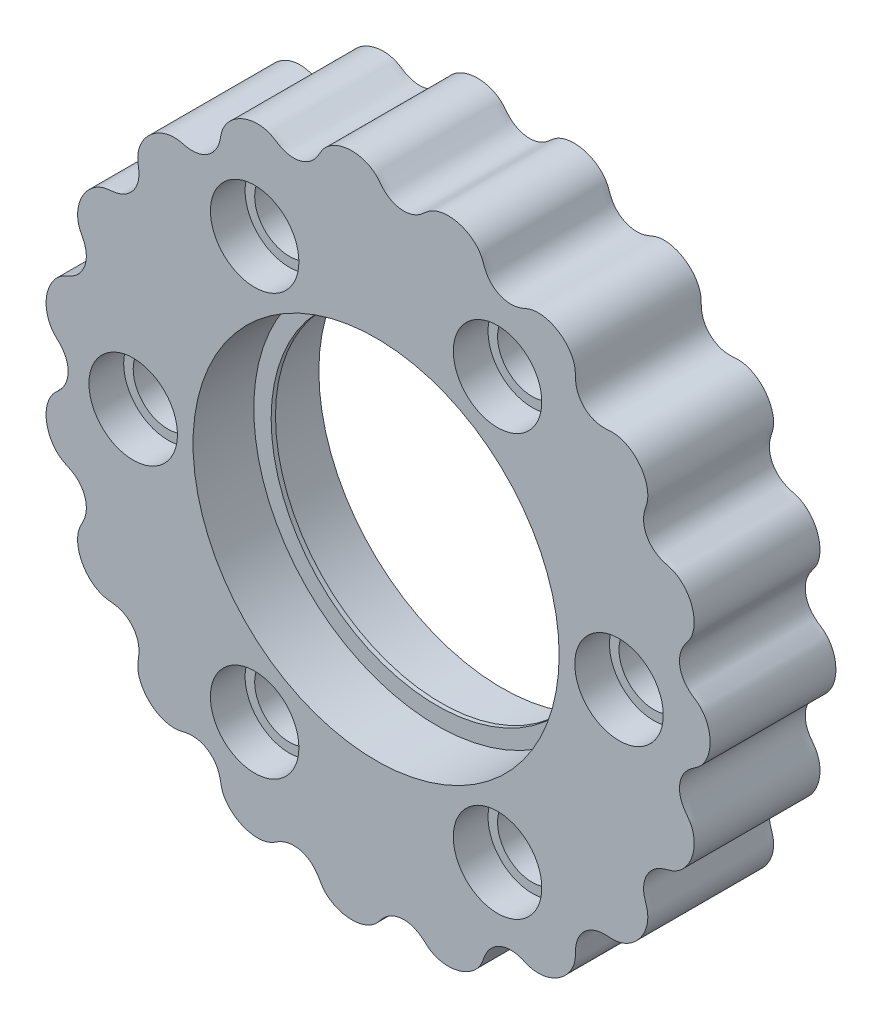
SolidWorks part; units mm, degrees
ref_plane "Front Plane" through (0, 0, 0) normal (0, 0, 1) x (1, 0, 0)
ref_plane "Top Plane" through (0, 0, 0) normal (0, 1, 0) x (1, 0, 0)
ref_plane "Right Plane" through (0, 0, 0) normal (1, 0, 0) x (0, 0, -1)
ref_axis "Axis1" through (0, 0, 55) along (0, 0, -1)
sketch "LobeBaseSketch" plane through (0, 0, 0) normal (0, 0, 1) x (1, 0, 0)
  spline S0 degree 3 poles (38.4912, -0.3506) (38.5044, 0) (38.4912, 0.3506) (38.4519, 0.6962) (38.3879, 1.0318) (38.3014, 1.353) (38.1951, 1.6558) (38.0727, 1.9368) (37.9379, 2.1933) (37.7949, 2.4237) (37.648, 2.6273) (37.5008, 2.8045) (37.3566, 2.9569) (37.2168, 3.0875) (37.0808, 3.2008) (36.9438, 3.304) (36.794, 3.4082) (36.6064, 3.5339) (36.3332, 3.724) (35.9067, 4.0748) (35.3443, 4.7509) (34.9315, 5.829) (34.9719, 6.9828) (35.2843, 7.8049) (35.5737, 8.2752) (35.7704, 8.5437) (35.9071, 8.7234) (36.0149, 8.8707) (36.111, 9.0127) (36.2028, 9.1641) (36.2926, 9.333) (36.3796, 9.5239) (36.4612, 9.7393) (36.5341, 9.9796) (36.5944, 10.2439) (36.6386, 10.5303) (36.6633, 10.8358) (36.6655, 11.1567) (36.643, 11.4886) (36.5945, 11.8269) (36.5195, 12.1665) (36.4181, 12.5024) (36.2918, 12.8297) (36.1425, 13.1438) (35.973, 13.4405) (35.7868, 13.7162) (35.588, 13.968) (35.3809, 14.194) (35.1701, 14.3929) (34.9601, 14.5644) (34.755, 14.7093) (34.5583, 14.8291) (34.3724, 14.9264) (34.1978, 15.0045) (34.0324, 15.0675) (33.8693, 15.1206) (33.6938, 15.1705) (33.4755, 15.2285) (33.1554, 15.3195) (32.6381, 15.5129) (31.8866, 15.9698) (31.1462, 16.8555) (30.8097, 17.9598) (30.8382, 18.8388) (30.9593, 19.3776) (31.0581, 19.6954) (31.129, 19.9098) (31.1832, 20.0841) (31.228, 20.2496) (31.2657, 20.4226) (31.2958, 20.6115) (31.316, 20.8203) (31.3233, 21.0505) (31.3142, 21.3015) (31.2855, 21.5711) (31.2343, 21.8563) (31.1584, 22.1533) (31.0562, 22.4575) (30.9272, 22.7641) (30.7716, 23.0683) (30.5903, 23.3651) (30.3854, 23.6499) (30.1596, 23.9184) (29.9164, 24.167) (29.6597, 24.3926) (29.3941, 24.5929) (29.1243, 24.7666) (28.8551, 24.9131) (28.5911, 25.0327) (28.3368, 25.1268) (28.0958, 25.1972) (27.8709, 25.2467) (27.6634, 25.2783) (27.4729, 25.2955) (27.296, 25.3014) (27.1245, 25.2987) (26.9423, 25.2889) (26.717, 25.2728) (26.3847, 25.255) (25.8327, 25.2699) (24.9735, 25.4581) (23.9856, 26.0553) (23.3088, 26.9905) (23.0504, 27.8312) (22.9899, 28.3801) (22.9802, 28.7128) (22.9777, 28.9386) (22.9723, 29.121) (22.9609, 29.2921) (22.9404, 29.468) (22.9076, 29.6564) (22.8589, 29.8605) (22.791, 30.0806) (22.7009, 30.315) (22.5862, 30.5607) (22.4452, 30.8138) (22.277, 31.07) (22.0816, 31.3246) (21.86, 31.5728) (21.614, 31.8099) (21.3462, 32.0318) (21.0599, 32.2346) (20.7592, 32.4153) (20.4484, 32.5714) (20.1324, 32.7015) (19.8162, 32.8047) (19.5046, 32.8813) (19.2024, 32.9325) (18.9139, 32.9599) (18.6428, 32.9663) (18.392, 32.9546) (18.1632, 32.9284) (17.9567, 32.891) (17.7709, 32.8454) (17.6017, 32.7935) (17.4404, 32.7353) (17.2712, 32.6668) (17.0633, 32.5785) (16.7548, 32.4537) (16.2278, 32.2886) (15.3542, 32.1876) (14.2259, 32.4317) (13.2821, 33.0965) (12.7647, 33.8077) (12.5293, 34.3072) (12.4121, 34.6187) (12.3363, 34.8315) (12.2721, 35.0023) (12.2057, 35.1604) (12.1292, 35.3201) (12.0369, 35.4876) (11.9246, 35.6649) (11.789, 35.851) (11.6277, 36.0434) (11.4394, 36.2385) (11.2238, 36.4322) (10.9815, 36.6199) (10.7141, 36.7972) (10.4239, 36.96) (10.1142, 37.1044) (9.7889, 37.2273) (9.4523, 37.3262) (9.1092, 37.3994) (8.7645, 37.4462) (8.4234, 37.4666) (8.0908, 37.4615) (7.7712, 37.4329) (7.4688, 37.3831) (7.187, 37.3154) (6.9285, 37.2334) (6.6951, 37.1409) (6.4872, 37.0418) (6.3041, 36.9394) (6.1432, 36.8359) (5.9999, 36.7319) (5.8663, 36.6245) (5.7285, 36.5048) (5.5606, 36.3538) (5.3093, 36.1356) (4.8645, 35.8083) (4.071, 35.4291) (2.9245, 35.2936) (1.816, 35.6159) (1.0957, 36.1206) (0.7109, 36.5166) (0.4989, 36.7732) (0.3582, 36.9498) (0.2419, 37.0905) (0.1278, 37.2185) (0.0036, 37.3447) (-0.1381, 37.4732) (-0.3018, 37.6044) (-0.4906, 37.7363) (-0.7056, 37.866) (-0.9471, 37.9894) (-1.2139, 38.1026) (-1.504, 38.2014) (-1.8145, 38.2823) (-2.1418, 38.342) (-2.4816, 38.3781) (-2.8292, 38.3887) (-3.1797, 38.3729) (-3.528, 38.3308) (-3.8691, 38.2631) (-4.1983, 38.1716) (-4.5113, 38.0588) (-4.8043, 37.928) (-5.0742, 37.7827) (-5.3187, 37.6272) (-5.5365, 37.4657) (-5.7273, 37.3024) (-5.8918, 37.1412) (-6.0317, 36.9848) (-6.1503, 36.8347) (-6.252, 36.6899) (-6.3435, 36.5448) (-6.435, 36.3869) (-6.5447, 36.1895) (-6.7116, 35.9016) (-7.026, 35.4476) (-7.6534, 34.8313) (-8.6938, 34.3309) (-9.8469, 34.2758) (-10.692, 34.5192) (-11.1846, 34.7688) (-11.4684, 34.9427) (-11.6588, 35.064) (-11.8145, 35.1594) (-11.964, 35.2434) (-12.1224, 35.3224) (-12.2981, 35.3979) (-12.4956, 35.4688) (-12.717, 35.5324) (-12.9625, 35.5852) (-13.2309, 35.6235) (-13.52, 35.6439) (-13.8265, 35.6432) (-14.1464, 35.6189) (-14.4754, 35.5691) (-14.8084, 35.4929) (-15.1407, 35.39) (-15.4671, 35.2613) (-15.7828, 35.1084) (-16.0835, 34.9336) (-16.3652, 34.7402) (-16.6246, 34.5319) (-16.8592, 34.313) (-17.0673, 34.0879) (-17.248, 33.8614) (-17.4016, 33.638) (-17.5291, 33.4216) (-17.6322, 33.2157) (-17.7138, 33.0224) (-17.7772, 32.8419) (-17.8264, 32.6719) (-17.8659, 32.505) (-17.9011, 32.3259) (-17.9409, 32.1036) (-18.0052, 31.7771) (-18.1551, 31.2456) (-18.5484, 30.4589) (-19.3699, 29.6479) (-20.4427, 29.2214) (-21.321, 29.1772) (-21.868, 29.2533) (-22.1929, 29.3256) (-22.4124, 29.3786) (-22.5906, 29.4182) (-22.7593, 29.4491) (-22.9347, 29.4724) (-23.1254, 29.4868) (-23.3353, 29.4897) (-23.5653, 29.478) (-23.8146, 29.4482) (-24.0809, 29.3973) (-24.361, 29.3227) (-24.6506, 29.2225) (-24.9454, 29.0956) (-25.2403, 28.9418) (-25.5306, 28.7615) (-25.8114, 28.5563) (-26.0783, 28.3286) (-26.3273, 28.0814) (-26.555, 27.8185) (-26.7586, 27.5441) (-26.9363, 27.2629) (-27.0871, 26.9796) (-27.2108, 26.6992) (-27.3083, 26.4263) (-27.381, 26.1651) (-27.4313, 25.9191) (-27.462, 25.6908) (-27.4764, 25.4815) (-27.4778, 25.2902) (-27.4691, 25.1134) (-27.4522, 24.9428) (-27.4274, 24.7619) (-27.3928, 24.5388) (-27.3476, 24.209) (-27.3169, 23.6577) (-27.4334, 22.7859) (-27.947, 21.7521) (-28.8232, 21.0004) (-29.6396, 20.6734) (-30.1817, 20.5678) (-30.5124, 20.5307) (-30.7372, 20.5095) (-30.9186, 20.4891) (-31.0882, 20.4635) (-31.2617, 20.4286) (-31.4468, 20.3803) (-31.6462, 20.3149) (-31.8599, 20.2291) (-32.0861, 20.12) (-32.3214, 19.9854) (-32.5621, 19.8239) (-32.8035, 19.6351) (-33.0411, 19.4194) (-33.2701, 19.1781) (-33.4861, 18.9133) (-33.6851, 18.6281) (-33.8636, 18.3261) (-34.0189, 18.0114) (-34.1488, 17.6888) (-34.2523, 17.3632) (-34.3291, 17.0395) (-34.3797, 16.7226) (-34.4057, 16.4172) (-34.4092, 16.1275) (-34.3932, 15.8568) (-34.3609, 15.6078) (-34.3158, 15.3819) (-34.2615, 15.1792) (-34.2007, 14.9979) (-34.135, 14.8335) (-34.0637, 14.6776) (-33.9815, 14.5146) (-33.8763, 14.3148) (-33.7265, 14.0176) (-33.5184, 13.506) (-33.3456, 12.6437) (-33.4957, 11.4991) (-34.0803, 10.5036) (-34.7463, 9.9293) (-35.2247, 9.6534) (-35.5255, 9.5109) (-35.7312, 9.4178) (-35.8962, 9.3397) (-36.0483, 9.2605) (-36.201, 9.171) (-36.3604, 9.0653) (-36.5278, 8.9387) (-36.7021, 8.7882) (-36.8805, 8.6115) (-37.0594, 8.4078) (-37.2346, 8.1769) (-37.4017, 7.9199) (-37.5563, 7.6388) (-37.6946, 7.3362) (-37.8129, 7.0156) (-37.9085, 6.6813) (-37.9793, 6.3376) (-38.0239, 5.9896) (-38.0421, 5.6423) (-38.0342, 5.3007) (-38.0017, 4.9696) (-37.9467, 4.6535) (-37.8722, 4.3562) (-37.7814, 4.081) (-37.6784, 3.8302) (-37.5669, 3.6051) (-37.451, 3.4062) (-37.3338, 3.2321) (-37.2174, 3.0803) (-37.1019, 2.9462) (-36.9838, 2.8218) (-36.8532, 2.6944) (-36.6888, 2.5395) (-36.4506, 2.3071) (-36.0877, 1.8908) (-35.6442, 1.1313) (-35.4145, 0) (-35.6442, -1.1313) (-36.0877, -1.8908) (-36.4506, -2.3071) (-36.6888, -2.5395) (-36.8532, -2.6944) (-36.9838, -2.8218) (-37.1019, -2.9462) (-37.2174, -3.0803) (-37.3338, -3.2321) (-37.451, -3.4062) (-37.5669, -3.6051) (-37.6784, -3.8302) (-37.7814, -4.081) (-37.8722, -4.3562) (-37.9467, -4.6535) (-38.0017, -4.9696) (-38.0342, -5.3007) (-38.0421, -5.6423) (-38.0239, -5.9896) (-37.9793, -6.3376) (-37.9085, -6.6813) (-37.8129, -7.0156) (-37.6946, -7.3362) (-37.5563, -7.6388) (-37.4017, -7.9199) (-37.2346, -8.1769) (-37.0594, -8.4078) (-36.8805, -8.6115) (-36.7021, -8.7882) (-36.5278, -8.9387) (-36.3604, -9.0653) (-36.201, -9.171) (-36.0483, -9.2605) (-35.8962, -9.3397) (-35.7312, -9.4178) (-35.5255, -9.5109) (-35.2247, -9.6534) (-34.7463, -9.9293) (-34.0803, -10.5036) (-33.4957, -11.4991) (-33.3456, -12.6437) (-33.5184, -13.506) (-33.7265, -14.0176) (-33.8763, -14.3148) (-33.9815, -14.5146) (-34.0637, -14.6776) (-34.135, -14.8335) (-34.2007, -14.9979) (-34.2615, -15.1792) (-34.3158, -15.3819) (-34.3609, -15.6078) (-34.3932, -15.8568) (-34.4092, -16.1275) (-34.4057, -16.4172) (-34.3797, -16.7226) (-34.3291, -17.0395) (-34.2523, -17.3632) (-34.1488, -17.6888) (-34.0189, -18.0114) (-33.8636, -18.3261) (-33.6851, -18.6281) (-33.4861, -18.9133) (-33.2701, -19.1781) (-33.0411, -19.4194) (-32.8035, -19.6351) (-32.5621, -19.8239) (-32.3214, -19.9854) (-32.0861, -20.12) (-31.8599, -20.2291) (-31.6462, -20.3149) (-31.4468, -20.3803) (-31.2617, -20.4286) (-31.0882, -20.4635) (-30.9186, -20.4891) (-30.7372, -20.5095) (-30.5124, -20.5307) (-30.1817, -20.5678) (-29.6396, -20.6734) (-28.8232, -21.0004) (-27.947, -21.7521) (-27.4334, -22.7859) (-27.3169, -23.6577) (-27.3476, -24.209) (-27.3928, -24.5388) (-27.4274, -24.7619) (-27.4522, -24.9428) (-27.4691, -25.1134) (-27.4778, -25.2902) (-27.4764, -25.4815) (-27.462, -25.6908) (-27.4313, -25.9191) (-27.381, -26.1651) (-27.3083, -26.4263) (-27.2108, -26.6992) (-27.0871, -26.9796) (-26.9363, -27.2629) (-26.7586, -27.5441) (-26.555, -27.8185) (-26.3273, -28.0814) (-26.0783, -28.3286) (-25.8114, -28.5563) (-25.5306, -28.7615) (-25.2403, -28.9418) (-24.9454, -29.0956) (-24.6506, -29.2225) (-24.361, -29.3227) (-24.0809, -29.3973) (-23.8146, -29.4482) (-23.5653, -29.478) (-23.3353, -29.4897) (-23.1254, -29.4868) (-22.9347, -29.4724) (-22.7593, -29.4491) (-22.5906, -29.4182) (-22.4124, -29.3786) (-22.1929, -29.3256) (-21.868, -29.2533) (-21.321, -29.1772) (-20.4427, -29.2214) (-19.3699, -29.6479) (-18.5484, -30.4589) (-18.1551, -31.2456) (-18.0052, -31.7771) (-17.9409, -32.1036) (-17.9011, -32.3259) (-17.8659, -32.505) (-17.8264, -32.6719) (-17.7772, -32.8419) (-17.7138, -33.0224) (-17.6322, -33.2157) (-17.5291, -33.4216) (-17.4016, -33.638) (-17.248, -33.8614) (-17.0673, -34.0879) (-16.8592, -34.313) (-16.6246, -34.5319) (-16.3652, -34.7402) (-16.0835, -34.9336) (-15.7828, -35.1084) (-15.4671, -35.2613) (-15.1407, -35.39) (-14.8084, -35.4929) (-14.4754, -35.5691) (-14.1464, -35.6189) (-13.8265, -35.6432) (-13.52, -35.6439) (-13.2309, -35.6235) (-12.9625, -35.5852) (-12.717, -35.5324) (-12.4956, -35.4688) (-12.2981, -35.3979) (-12.1224, -35.3224) (-11.964, -35.2434) (-11.8145, -35.1594) (-11.6588, -35.064) (-11.4684, -34.9427) (-11.1846, -34.7688) (-10.692, -34.5192) (-9.8469, -34.2758) (-8.6938, -34.3309) (-7.6534, -34.8313) (-7.026, -35.4476) (-6.7116, -35.9016) (-6.5447, -36.1895) (-6.435, -36.3869) (-6.3435, -36.5448) (-6.252, -36.6899) (-6.1503, -36.8347) (-6.0317, -36.9848) (-5.8918, -37.1412) (-5.7273, -37.3024) (-5.5365, -37.4657) (-5.3187, -37.6272) (-5.0742, -37.7827) (-4.8043, -37.928) (-4.5113, -38.0588) (-4.1983, -38.1716) (-3.8691, -38.2631) (-3.528, -38.3308) (-3.1797, -38.3729) (-2.8292, -38.3887) (-2.4816, -38.3781) (-2.1418, -38.342) (-1.8145, -38.2823) (-1.504, -38.2014) (-1.2139, -38.1026) (-0.9471, -37.9894) (-0.7056, -37.866) (-0.4906, -37.7363) (-0.3018, -37.6044) (-0.1381, -37.4732) (0.0036, -37.3447) (0.1278, -37.2185) (0.2419, -37.0905) (0.3582, -36.9498) (0.4989, -36.7732) (0.7109, -36.5166) (1.0957, -36.1206) (1.816, -35.6159) (2.9245, -35.2936) (4.071, -35.4291) (4.8645, -35.8083) (5.3093, -36.1356) (5.5606, -36.3538) (5.7285, -36.5048) (5.8663, -36.6245) (5.9999, -36.7319) (6.1432, -36.8359) (6.3041, -36.9394) (6.4872, -37.0418) (6.6951, -37.1409) (6.9285, -37.2334) (7.187, -37.3154) (7.4688, -37.3831) (7.7712, -37.4329) (8.0908, -37.4615) (8.4234, -37.4666) (8.7645, -37.4462) (9.1092, -37.3994) (9.4523, -37.3262) (9.7889, -37.2273) (10.1142, -37.1044) (10.4239, -36.96) (10.7141, -36.7972) (10.9815, -36.6199) (11.2238, -36.4322) (11.4394, -36.2385) (11.6277, -36.0434) (11.789, -35.851) (11.9246, -35.6649) (12.0369, -35.4876) (12.1292, -35.3201) (12.2057, -35.1604) (12.2721, -35.0023) (12.3363, -34.8315) (12.4121, -34.6187) (12.5293, -34.3072) (12.7647, -33.8077) (13.2821, -33.0965) (14.2259, -32.4317) (15.3542, -32.1876) (16.2278, -32.2886) (16.7548, -32.4537) (17.0633, -32.5785) (17.2712, -32.6668) (17.4404, -32.7353) (17.6017, -32.7935) (17.7709, -32.8454) (17.9567, -32.891) (18.1632, -32.9284) (18.392, -32.9546) (18.6428, -32.9663) (18.9139, -32.9599) (19.2024, -32.9325) (19.5046, -32.8813) (19.8162, -32.8047) (20.1324, -32.7015) (20.4484, -32.5714) (20.7592, -32.4153) (21.0599, -32.2346) (21.3462, -32.0318) (21.614, -31.8099) (21.86, -31.5728) (22.0816, -31.3246) (22.277, -31.07) (22.4452, -30.8138) (22.5862, -30.5607) (22.7009, -30.315) (22.791, -30.0806) (22.8589, -29.8605) (22.9076, -29.6564) (22.9404, -29.468) (22.9609, -29.2921) (22.9723, -29.121) (22.9777, -28.9386) (22.9802, -28.7128) (22.9899, -28.3801) (23.0504, -27.8312) (23.3088, -26.9905) (23.9856, -26.0553) (24.9735, -25.4581) (25.8327, -25.2699) (26.3847, -25.255) (26.717, -25.2728) (26.9423, -25.2889) (27.1245, -25.2987) (27.296, -25.3014) (27.4729, -25.2955) (27.6634, -25.2783) (27.8709, -25.2467) (28.0958, -25.1972) (28.3368, -25.1268) (28.5911, -25.0327) (28.8551, -24.9131) (29.1243, -24.7666) (29.3941, -24.5929) (29.6597, -24.3926) (29.9164, -24.167) (30.1596, -23.9184) (30.3854, -23.6499) (30.5903, -23.3651) (30.7716, -23.0683) (30.9272, -22.7641) (31.0562, -22.4575) (31.1584, -22.1533) (31.2343, -21.8563) (31.2855, -21.5711) (31.3142, -21.3015) (31.3233, -21.0505) (31.316, -20.8203) (31.2958, -20.6115) (31.2657, -20.4226) (31.228, -20.2496) (31.1832, -20.0841) (31.129, -19.9098) (31.0581, -19.6954) (30.9593, -19.3776) (30.8382, -18.8388) (30.8097, -17.9598) (31.1462, -16.8555) (31.8866, -15.9698) (32.6381, -15.5129) (33.1554, -15.3195) (33.4755, -15.2285) (33.6938, -15.1705) (33.8693, -15.1206) (34.0324, -15.0675) (34.1978, -15.0045) (34.3724, -14.9264) (34.5583, -14.8291) (34.755, -14.7093) (34.9601, -14.5644) (35.1701, -14.3929) (35.3809, -14.194) (35.588, -13.968) (35.7868, -13.7162) (35.973, -13.4405) (36.1425, -13.1438) (36.2918, -12.8297) (36.4181, -12.5024) (36.5195, -12.1665) (36.5945, -11.8269) (36.643, -11.4886) (36.6655, -11.1567) (36.6633, -10.8358) (36.6386, -10.5303) (36.5944, -10.2439) (36.5341, -9.9796) (36.4612, -9.7393) (36.3796, -9.5239) (36.2926, -9.333) (36.2028, -9.1641) (36.111, -9.0127) (36.0149, -8.8707) (35.9071, -8.7234) (35.7704, -8.5437) (35.5737, -8.2752) (35.2843, -7.8049) (34.9719, -6.9828) (34.9315, -5.829) (35.3443, -4.7509) (35.9067, -4.0748) (36.3332, -3.724) (36.6064, -3.5339) (36.794, -3.4082) (36.9438, -3.304) (37.0808, -3.2008) (37.2168, -3.0875) (37.3566, -2.9569) (37.5008, -2.8045) (37.648, -2.6273) (37.7949, -2.4237) (37.9379, -2.1933) (38.0727, -1.9368) (38.1951, -1.6558) (38.3014, -1.353) (38.3879, -1.0318) (38.4519, -0.6962) (38.4912, -0.3506) (38.5044, 0) (38.4912, 0.3506) knots -0.003877 -0.002604 -0.001308 0 0.001308 0.002604 0.003877 0.005117 0.006313 0.007454 0.008534 0.009543 0.010478 0.011334 0.012112 0.012818 0.013466 0.014086 0.014731 0.015503 0.016606 0.018444 0.021651 0.026316 0.03098 0.034188 0.036026 0.037129 0.037901 0.038546 0.039165 0.039814 0.04052 0.041298 0.042154 0.043088 0.044098 0.045177 0.046319 0.047515 0.048754 0.050028 0.051324 0.052632 0.053939 0.055235 0.056509 0.057748 0.058944 0.060086 0.061165 0.062175 0.063109 0.063965 0.064743 0.065449 0.066098 0.066718 0.067362 0.068134 0.069238 0.071075 0.074283 0.078947 0.083612 0.08682 0.088657 0.08976 0.090533 0.091177 0.091797 0.092445 0.093152 0.09393 0.094785 0.09572 0.096729 0.097809 0.098951 0.100146 0.101386 0.102659 0.103956 0.105263 0.106571 0.107867 0.10914 0.11038 0.111576 0.112718 0.113797 0.114807 0.115741 0.116597 0.117375 0.118081 0.11873 0.119349 0.119994 0.120766 0.121869 0.123707 0.126914 0.131579 0.136243 0.139451 0.141289 0.142392 0.143164 0.143809 0.144428 0.145077 0.145783 0.146561 0.147417 0.148351 0.149361 0.15044 0.151582 0.152778 0.154018 0.155291 0.156587 0.157895 0.159202 0.160498 0.161772 0.163012 0.164207 0.165349 0.166429 0.167438 0.168372 0.169228 0.170006 0.170712 0.171361 0.171981 0.172625 0.173398 0.174501 0.176338 0.179546 0.184211 0.188875 0.192083 0.19392 0.195023 0.195796 0.19644 0.19706 0.197709 0.198415 0.199193 0.200049 0.200983 0.201992 0.203072 0.204214 0.205409 0.206649 0.207923 0.209219 0.210526 0.211834 0.21313 0.214403 0.215643 0.216839 0.217981 0.21906 0.22007 0.221004 0.22186 0.222638 0.223344 0.223993 0.224612 0.225257 0.226029 0.227132 0.22897 0.232178 0.236842 0.241507 0.244714 0.246552 0.247655 0.248427 0.249072 0.249692 0.25034 0.251046 0.251824 0.25268 0.253614 0.254624 0.255703 0.256845 0.258041 0.259281 0.260554 0.26185 0.263158 0.264465 0.265762 0.267035 0.268275 0.26947 0.270612 0.271692 0.272701 0.273636 0.274491 0.275269 0.275976 0.276624 0.277244 0.277888 0.278661 0.279764 0.281602 0.284809 0.289474 0.294138 0.297346 0.299183 0.300287 0.301059 0.301703 0.302323 0.302972 0.303678 0.304456 0.305312 0.306246 0.307256 0.308335 0.309477 0.310673 0.311912 0.313186 0.314482 0.315789 0.317097 0.318393 0.319667 0.320906 0.322102 0.323244 0.324323 0.325333 0.326267 0.327123 0.327901 0.328607 0.329256 0.329876 0.33052 0.331292 0.332395 0.334233 0.337441 0.342105 0.34677 0.349977 0.351815 0.352918 0.35369 0.354335 0.354955 0.355603 0.35631 0.357088 0.357943 0.358878 0.359887 0.360967 0.362109 0.363304 0.364544 0.365817 0.367113 0.368421 0.369729 0.371025 0.372298 0.373538 0.374734 0.375875 0.376955 0.377965 0.378899 0.379755 0.380533 0.381239 0.381887 0.382507 0.383152 0.383924 0.385027 0.386865 0.390072 0.394737 0.399401 0.402609 0.404447 0.40555 0.406322 0.406967 0.407586 0.408235 0.408941 0.409719 0.410575 0.411509 0.412519 0.413598 0.41474 0.415936 0.417176 0.418449 0.419745 0.421053 0.42236 0.423656 0.42493 0.426169 0.427365 0.428507 0.429586 0.430596 0.43153 0.432386 0.433164 0.43387 0.434519 0.435139 0.435783 0.436556 0.437659 0.439496 0.442704 0.447368 0.452033 0.455241 0.457078 0.458181 0.458954 0.459598 0.460218 0.460867 0.461573 0.462351 0.463207 0.464141 0.46515 0.46623 0.467372 0.468567 0.469807 0.471081 0.472377 0.473684 0.474992 0.476288 0.477561 0.478801 0.479997 0.481139 0.482218 0.483228 0.484162 0.485018 0.485796 0.486502 0.487151 0.48777 0.488415 0.489187 0.49029 0.492128 0.495336 0.5 0.504664 0.507872 0.50971 0.510813 0.511585 0.51223 0.512849 0.513498 0.514204 0.514982 0.515838 0.516772 0.517782 0.518861 0.520003 0.521199 0.522439 0.523712 0.525008 0.526316 0.527623 0.528919 0.530193 0.531433 0.532628 0.53377 0.53485 0.535859 0.536793 0.537649 0.538427 0.539133 0.539782 0.540402 0.541046 0.541819 0.542922 0.544759 0.547967 0.552632 0.557296 0.560504 0.562341 0.563444 0.564217 0.564861 0.565481 0.56613 0.566836 0.567614 0.56847 0.569404 0.570414 0.571493 0.572635 0.573831 0.57507 0.576344 0.57764 0.578947 0.580255 0.581551 0.582824 0.584064 0.58526 0.586402 0.587481 0.588491 0.589425 0.590281 0.591059 0.591765 0.592414 0.593033 0.593678 0.59445 0.595553 0.597391 0.600599 0.605263 0.609928 0.613135 0.614973 0.616076 0.616848 0.617493 0.618113 0.618761 0.619467 0.620245 0.621101 0.622035 0.623045 0.624125 0.625266 0.626462 0.627702 0.628975 0.630271 0.631579 0.632887 0.634183 0.635456 0.636696 0.637891 0.639033 0.640113 0.641122 0.642057 0.642912 0.64369 0.644397 0.645045 0.645665 0.64631 0.647082 0.648185 0.650023 0.65323 0.657895 0.662559 0.665767 0.667605 0.668708 0.66948 0.670124 0.670744 0.671393 0.672099 0.672877 0.673733 0.674667 0.675677 0.676756 0.677898 0.679094 0.680333 0.681607 0.682903 0.684211 0.685518 0.686814 0.688088 0.689327 0.690523 0.691665 0.692744 0.693754 0.694688 0.695544 0.696322 0.697028 0.697677 0.698297 0.698941 0.699713 0.700817 0.702654 0.705862 0.710526 0.715191 0.718398 0.720236 0.721339 0.722112 0.722756 0.723376 0.724024 0.724731 0.725509 0.726364 0.727299 0.728308 0.729388 0.73053 0.731725 0.732965 0.734238 0.735535 0.736842 0.73815 0.739446 0.740719 0.741959 0.743155 0.744297 0.745376 0.746386 0.74732 0.748176 0.748954 0.74966 0.750308 0.750928 0.751573 0.752345 0.753448 0.755286 0.758493 0.763158 0.767822 0.77103 0.772868 0.773971 0.774743 0.775388 0.776007 0.776656 0.777362 0.77814 0.778996 0.77993 0.78094 0.782019 0.783161 0.784357 0.785597 0.78687 0.788166 0.789474 0.790781 0.792077 0.793351 0.794591 0.795786 0.796928 0.798008 0.799017 0.799951 0.800807 0.801585 0.802291 0.80294 0.80356 0.804204 0.804977 0.80608 0.807917 0.811125 0.815789 0.820454 0.823662 0.825499 0.826602 0.827375 0.828019 0.828639 0.829288 0.829994 0.830772 0.831628 0.832562 0.833571 0.834651 0.835793 0.836988 0.838228 0.839502 0.840798 0.842105 0.843413 0.844709 0.845982 0.847222 0.848418 0.84956 0.850639 0.851649 0.852583 0.853439 0.854217 0.854923 0.855572 0.856191 0.856836 0.857608 0.858711 0.860549 0.863757 0.868421 0.873086 0.876293 0.878131 0.879234 0.880006 0.880651 0.88127 0.881919 0.882625 0.883403 0.884259 0.885193 0.886203 0.887282 0.888424 0.88962 0.89086 0.892133 0.893429 0.894737 0.896044 0.897341 0.898614 0.899854 0.901049 0.902191 0.903271 0.90428 0.905215 0.90607 0.906848 0.907555 0.908203 0.908823 0.909467 0.91024 0.911343 0.91318 0.916388 0.921053 0.925717 0.928925 0.930762 0.931866 0.932638 0.933282 0.933902 0.934551 0.935257 0.936035 0.936891 0.937825 0.938835 0.939914 0.941056 0.942252 0.943491 0.944765 0.946061 0.947368 0.948676 0.949972 0.951246 0.952485 0.953681 0.954823 0.955902 0.956912 0.957846 0.958702 0.95948 0.960186 0.960835 0.961454 0.962099 0.962871 0.963974 0.965812 0.96902 0.973684 0.978349 0.981556 0.983394 0.984497 0.985269 0.985914 0.986534 0.987182 0.987888 0.988666 0.989522 0.990457 0.991466 0.992546 0.993687 0.994883 0.996123 0.997396 0.998692 1 1.001308 1.002604 1.003877 only from (38.5, 0) to (38.5, 0)
extrude "LobeBase" add sketch "LobeBaseSketch" along normal blind 7.25 and the other way blind 7.25
sketch "AuxiliarySketchCycloidal01" plane through (0, 0, 0) normal (0, 0, 1) x (1, 0, 0)
  circle A0 centre (0, 0) radius 38 construction
  circle A1 centre (40, 0) radius 2 construction
  circle A2 centre (0, 0) radius 40 construction
  circle A3 centre (40, 0) radius 3 construction
  circle A4 centre (41.5, 0) radius 0.3 construction
  spline S0 degree 3 poles (41.5, 0) (41.5, 0.3843) (41.4568, 0.9578) (41.3145, 1.7041) (41.1697, 2.2415) (40.9899, 2.7537) (40.7798, 3.2358) (40.5445, 3.6835) (40.2901, 4.0936) (40.023, 4.4639) (39.7497, 4.7932) (39.4771, 5.0816) (39.2117, 5.3301) (38.96, 5.5408) (38.7277, 5.7169) (38.5202, 5.8624) (38.3419, 5.9822) (38.1959, 6.0818) (38.0845, 6.1679) (38.007, 6.248) (37.9674, 6.3356) (37.9764, 6.4314) (38.0237, 6.5323) (38.1012, 6.6499) (38.2068, 6.7915) (38.3366, 6.9628) (38.4856, 7.1678) (38.6481, 7.4097) (38.8178, 7.6907) (38.9881, 8.0119) (39.1523, 8.3732) (39.3039, 8.7734) (39.4363, 9.2104) (39.5437, 9.6809) (39.6209, 10.1807) (39.6631, 10.7049) (39.6668, 11.2477) (39.6293, 11.803) (39.5215, 12.5551) (39.3762, 13.1116) (39.2514, 13.475) knots 0 0 0 0 0.076019 0.113454 0.150205 0.18605 0.220775 0.25417 0.286039 0.316192 0.344454 0.370663 0.394671 0.41635 0.435595 0.452323 0.466491 0.478109 0.487286 0.494331 0.5 0.505669 0.512714 0.521891 0.533509 0.547677 0.564405 0.58365 0.605329 0.629337 0.655546 0.683808 0.713961 0.74583 0.779225 0.81395 0.849795 0.886546 0.923981 1 1 1 1 construction
sketch "Sketch5" plane through (0, 0, 7.25) normal (0, 0, 1) x (1, 0, 0)
  circle A0 centre (0, 0) radius 21.1
  dimension "D1" = 42.2
extrude "Cut-Extrude1" cut sketch "Sketch5" against normal blind 7
sketch "Sketch6" plane through (0, 0, -7.25) normal (0, 0, -1) x (-1, 0, 0)
  circle A0 centre (0, 0) radius 21.1
  dimension "D1" = 42.2
extrude "Cut-Extrude2" cut sketch "Sketch6" against normal blind 7
sketch "Sketch7" plane through (0, 0, 7.25) normal (0, 0, 1) x (1, 0, 0)
  circle A0 centre (0, 0) radius 19.1
  circle A1 centre (0, 0) radius 21.1 construction
  dimension "D1" = 2
extrude "Cut-Extrude3" cut sketch "Sketch7" against normal through all
sketch "Sketch8" plane through (0, 0, 7.25) normal (0, 0, 1) x (1, 0, 0)
  circle A0 centre (28, 0) radius 5.1
  dimension "D2" = 10.2
extrude "Cut-Extrude4" cut sketch "Sketch8" against normal blind 4
sketch "Sketch10" plane through (0, 0, -7.25) normal (0, 0, -1) x (-1, 0, 0)
  circle A0 centre (-28, 0) radius 4
  dimension "D1" = 8
extrude "Cut-Extrude5" cut sketch "Sketch10" against normal through all
pattern_circular "CirPattern1" count 6 over 360 about axis through (0, 0, 7.25) along (0, 0, 1) of "Cut-Extrude4", "Cut-Extrude5"
sketch "Sketch11" plane through (0, 0, 7.25) normal (0, 0, 1) x (1, 0, 0)
  line L0 (38.5, 0) -> (-35.5, 0) construction
  spline S0 degree 3 poles (38.4912, -0.3506) (38.5044, 0) (38.4912, 0.3506) (38.4519, 0.6962) (38.3879, 1.0318) (38.3014, 1.353) (38.1951, 1.6558) (38.0727, 1.9368) (37.9379, 2.1933) (37.7949, 2.4237) (37.648, 2.6273) (37.5008, 2.8045) (37.3566, 2.9569) (37.2168, 3.0875) (37.0808, 3.2008) (36.9438, 3.304) (36.794, 3.4082) (36.6064, 3.5339) (36.3332, 3.724) (35.9067, 4.0748) (35.3443, 4.7509) (34.9315, 5.829) (34.9719, 6.9828) (35.2843, 7.8049) (35.5737, 8.2752) (35.7704, 8.5437) (35.9071, 8.7234) (36.0149, 8.8707) (36.111, 9.0127) (36.2028, 9.1641) (36.2926, 9.333) (36.3796, 9.5239) (36.4612, 9.7393) (36.5341, 9.9796) (36.5944, 10.2439) (36.6386, 10.5303) (36.6633, 10.8358) (36.6655, 11.1567) (36.643, 11.4886) (36.5945, 11.8269) (36.5195, 12.1665) (36.4181, 12.5024) (36.2918, 12.8297) (36.1425, 13.1438) (35.973, 13.4405) (35.7868, 13.7162) (35.588, 13.968) (35.3809, 14.194) (35.1701, 14.3929) (34.9601, 14.5644) (34.755, 14.7093) (34.5583, 14.8291) (34.3724, 14.9264) (34.1978, 15.0045) (34.0324, 15.0675) (33.8693, 15.1206) (33.6938, 15.1705) (33.4755, 15.2285) (33.1554, 15.3195) (32.6381, 15.5129) (31.8866, 15.9698) (31.1462, 16.8555) (30.8097, 17.9598) (30.8382, 18.8388) (30.9593, 19.3776) (31.0581, 19.6954) (31.129, 19.9098) (31.1832, 20.0841) (31.228, 20.2496) (31.2657, 20.4226) (31.2958, 20.6115) (31.316, 20.8203) (31.3233, 21.0505) (31.3142, 21.3015) (31.2855, 21.5711) (31.2343, 21.8563) (31.1584, 22.1533) (31.0562, 22.4575) (30.9272, 22.7641) (30.7716, 23.0683) (30.5903, 23.3651) (30.3854, 23.6499) (30.1596, 23.9184) (29.9164, 24.167) (29.6597, 24.3926) (29.3941, 24.5929) (29.1243, 24.7666) (28.8551, 24.9131) (28.5911, 25.0327) (28.3368, 25.1268) (28.0958, 25.1972) (27.8709, 25.2467) (27.6634, 25.2783) (27.4729, 25.2955) (27.296, 25.3014) (27.1245, 25.2987) (26.9423, 25.2889) (26.717, 25.2728) (26.3847, 25.255) (25.8327, 25.2699) (24.9735, 25.4581) (23.9856, 26.0553) (23.3088, 26.9905) (23.0504, 27.8312) (22.9899, 28.3801) (22.9802, 28.7128) (22.9777, 28.9386) (22.9723, 29.121) (22.9609, 29.2921) (22.9404, 29.468) (22.9076, 29.6564) (22.8589, 29.8605) (22.791, 30.0806) (22.7009, 30.315) (22.5862, 30.5607) (22.4452, 30.8138) (22.277, 31.07) (22.0816, 31.3246) (21.86, 31.5728) (21.614, 31.8099) (21.3462, 32.0318) (21.0599, 32.2346) (20.7592, 32.4153) (20.4484, 32.5714) (20.1324, 32.7015) (19.8162, 32.8047) (19.5046, 32.8813) (19.2024, 32.9325) (18.9139, 32.9599) (18.6428, 32.9663) (18.392, 32.9546) (18.1632, 32.9284) (17.9567, 32.891) (17.7709, 32.8454) (17.6017, 32.7935) (17.4404, 32.7353) (17.2712, 32.6668) (17.0633, 32.5785) (16.7548, 32.4537) (16.2278, 32.2886) (15.3542, 32.1876) (14.2259, 32.4317) (13.2821, 33.0965) (12.7647, 33.8077) (12.5293, 34.3072) (12.4121, 34.6187) (12.3363, 34.8315) (12.2721, 35.0023) (12.2057, 35.1604) (12.1292, 35.3201) (12.0369, 35.4876) (11.9246, 35.6649) (11.789, 35.851) (11.6277, 36.0434) (11.4394, 36.2385) (11.2238, 36.4322) (10.9815, 36.6199) (10.7141, 36.7972) (10.4239, 36.96) (10.1142, 37.1044) (9.7889, 37.2273) (9.4523, 37.3262) (9.1092, 37.3994) (8.7645, 37.4462) (8.4234, 37.4666) (8.0908, 37.4615) (7.7712, 37.4329) (7.4688, 37.3831) (7.187, 37.3154) (6.9285, 37.2334) (6.6951, 37.1409) (6.4872, 37.0418) (6.3041, 36.9394) (6.1432, 36.8359) (5.9999, 36.7319) (5.8663, 36.6245) (5.7285, 36.5048) (5.5606, 36.3538) (5.3093, 36.1356) (4.8645, 35.8083) (4.071, 35.4291) (2.9245, 35.2936) (1.816, 35.6159) (1.0957, 36.1206) (0.7109, 36.5166) (0.4989, 36.7732) (0.3582, 36.9498) (0.2419, 37.0905) (0.1278, 37.2185) (0.0036, 37.3447) (-0.1381, 37.4732) (-0.3018, 37.6044) (-0.4906, 37.7363) (-0.7056, 37.866) (-0.9471, 37.9894) (-1.2139, 38.1026) (-1.504, 38.2014) (-1.8145, 38.2823) (-2.1418, 38.342) (-2.4816, 38.3781) (-2.8292, 38.3887) (-3.1797, 38.3729) (-3.528, 38.3308) (-3.8691, 38.2631) (-4.1983, 38.1716) (-4.5113, 38.0588) (-4.8043, 37.928) (-5.0742, 37.7827) (-5.3187, 37.6272) (-5.5365, 37.4657) (-5.7273, 37.3024) (-5.8918, 37.1412) (-6.0317, 36.9848) (-6.1503, 36.8347) (-6.252, 36.6899) (-6.3435, 36.5448) (-6.435, 36.3869) (-6.5447, 36.1895) (-6.7116, 35.9016) (-7.026, 35.4476) (-7.6534, 34.8313) (-8.6938, 34.3309) (-9.8469, 34.2758) (-10.692, 34.5192) (-11.1846, 34.7688) (-11.4684, 34.9427) (-11.6588, 35.064) (-11.8145, 35.1594) (-11.964, 35.2434) (-12.1224, 35.3224) (-12.2981, 35.3979) (-12.4956, 35.4688) (-12.717, 35.5324) (-12.9625, 35.5852) (-13.2309, 35.6235) (-13.52, 35.6439) (-13.8265, 35.6432) (-14.1464, 35.6189) (-14.4754, 35.5691) (-14.8084, 35.4929) (-15.1407, 35.39) (-15.4671, 35.2613) (-15.7828, 35.1084) (-16.0835, 34.9336) (-16.3652, 34.7402) (-16.6246, 34.5319) (-16.8592, 34.313) (-17.0673, 34.0879) (-17.248, 33.8614) (-17.4016, 33.638) (-17.5291, 33.4216) (-17.6322, 33.2157) (-17.7138, 33.0224) (-17.7772, 32.8419) (-17.8264, 32.6719) (-17.8659, 32.505) (-17.9011, 32.3259) (-17.9409, 32.1036) (-18.0052, 31.7771) (-18.1551, 31.2456) (-18.5484, 30.4589) (-19.3699, 29.6479) (-20.4427, 29.2214) (-21.321, 29.1772) (-21.868, 29.2533) (-22.1929, 29.3256) (-22.4124, 29.3786) (-22.5906, 29.4182) (-22.7593, 29.4491) (-22.9347, 29.4724) (-23.1254, 29.4868) (-23.3353, 29.4897) (-23.5653, 29.478) (-23.8146, 29.4482) (-24.0809, 29.3973) (-24.361, 29.3227) (-24.6506, 29.2225) (-24.9454, 29.0956) (-25.2403, 28.9418) (-25.5306, 28.7615) (-25.8114, 28.5563) (-26.0783, 28.3286) (-26.3273, 28.0814) (-26.555, 27.8185) (-26.7586, 27.5441) (-26.9363, 27.2629) (-27.0871, 26.9796) (-27.2108, 26.6992) (-27.3083, 26.4263) (-27.381, 26.1651) (-27.4313, 25.9191) (-27.462, 25.6908) (-27.4764, 25.4815) (-27.4778, 25.2902) (-27.4691, 25.1134) (-27.4522, 24.9428) (-27.4274, 24.7619) (-27.3928, 24.5388) (-27.3476, 24.209) (-27.3169, 23.6577) (-27.4334, 22.7859) (-27.947, 21.7521) (-28.8232, 21.0004) (-29.6396, 20.6734) (-30.1817, 20.5678) (-30.5124, 20.5307) (-30.7372, 20.5095) (-30.9186, 20.4891) (-31.0882, 20.4635) (-31.2617, 20.4286) (-31.4468, 20.3803) (-31.6462, 20.3149) (-31.8599, 20.2291) (-32.0861, 20.12) (-32.3214, 19.9854) (-32.5621, 19.8239) (-32.8035, 19.6351) (-33.0411, 19.4194) (-33.2701, 19.1781) (-33.4861, 18.9133) (-33.6851, 18.6281) (-33.8636, 18.3261) (-34.0189, 18.0114) (-34.1488, 17.6888) (-34.2523, 17.3632) (-34.3291, 17.0395) (-34.3797, 16.7226) (-34.4057, 16.4172) (-34.4092, 16.1275) (-34.3932, 15.8568) (-34.3609, 15.6078) (-34.3158, 15.3819) (-34.2615, 15.1792) (-34.2007, 14.9979) (-34.135, 14.8335) (-34.0637, 14.6776) (-33.9815, 14.5146) (-33.8763, 14.3148) (-33.7265, 14.0176) (-33.5184, 13.506) (-33.3456, 12.6437) (-33.4957, 11.4991) (-34.0803, 10.5036) (-34.7463, 9.9293) (-35.2247, 9.6534) (-35.5255, 9.5109) (-35.7312, 9.4178) (-35.8962, 9.3397) (-36.0483, 9.2605) (-36.201, 9.171) (-36.3604, 9.0653) (-36.5278, 8.9387) (-36.7021, 8.7882) (-36.8805, 8.6115) (-37.0594, 8.4078) (-37.2346, 8.1769) (-37.4017, 7.9199) (-37.5563, 7.6388) (-37.6946, 7.3362) (-37.8129, 7.0156) (-37.9085, 6.6813) (-37.9793, 6.3376) (-38.0239, 5.9896) (-38.0421, 5.6423) (-38.0342, 5.3007) (-38.0017, 4.9696) (-37.9467, 4.6535) (-37.8722, 4.3562) (-37.7814, 4.081) (-37.6784, 3.8302) (-37.5669, 3.6051) (-37.451, 3.4062) (-37.3338, 3.2321) (-37.2174, 3.0803) (-37.1019, 2.9462) (-36.9838, 2.8218) (-36.8532, 2.6944) (-36.6888, 2.5395) (-36.4506, 2.3071) (-36.0877, 1.8908) (-35.6442, 1.1313) (-35.4145, 0) (-35.6442, -1.1313) (-36.0877, -1.8908) (-36.4506, -2.3071) (-36.6888, -2.5395) (-36.8532, -2.6944) (-36.9838, -2.8218) (-37.1019, -2.9462) (-37.2174, -3.0803) (-37.3338, -3.2321) (-37.451, -3.4062) (-37.5669, -3.6051) (-37.6784, -3.8302) (-37.7814, -4.081) (-37.8722, -4.3562) (-37.9467, -4.6535) (-38.0017, -4.9696) (-38.0342, -5.3007) (-38.0421, -5.6423) (-38.0239, -5.9896) (-37.9793, -6.3376) (-37.9085, -6.6813) (-37.8129, -7.0156) (-37.6946, -7.3362) (-37.5563, -7.6388) (-37.4017, -7.9199) (-37.2346, -8.1769) (-37.0594, -8.4078) (-36.8805, -8.6115) (-36.7021, -8.7882) (-36.5278, -8.9387) (-36.3604, -9.0653) (-36.201, -9.171) (-36.0483, -9.2605) (-35.8962, -9.3397) (-35.7312, -9.4178) (-35.5255, -9.5109) (-35.2247, -9.6534) (-34.7463, -9.9293) (-34.0803, -10.5036) (-33.4957, -11.4991) (-33.3456, -12.6437) (-33.5184, -13.506) (-33.7265, -14.0176) (-33.8763, -14.3148) (-33.9815, -14.5146) (-34.0637, -14.6776) (-34.135, -14.8335) (-34.2007, -14.9979) (-34.2615, -15.1792) (-34.3158, -15.3819) (-34.3609, -15.6078) (-34.3932, -15.8568) (-34.4092, -16.1275) (-34.4057, -16.4172) (-34.3797, -16.7226) (-34.3291, -17.0395) (-34.2523, -17.3632) (-34.1488, -17.6888) (-34.0189, -18.0114) (-33.8636, -18.3261) (-33.6851, -18.6281) (-33.4861, -18.9133) (-33.2701, -19.1781) (-33.0411, -19.4194) (-32.8035, -19.6351) (-32.5621, -19.8239) (-32.3214, -19.9854) (-32.0861, -20.12) (-31.8599, -20.2291) (-31.6462, -20.3149) (-31.4468, -20.3803) (-31.2617, -20.4286) (-31.0882, -20.4635) (-30.9186, -20.4891) (-30.7372, -20.5095) (-30.5124, -20.5307) (-30.1817, -20.5678) (-29.6396, -20.6734) (-28.8232, -21.0004) (-27.947, -21.7521) (-27.4334, -22.7859) (-27.3169, -23.6577) (-27.3476, -24.209) (-27.3928, -24.5388) (-27.4274, -24.7619) (-27.4522, -24.9428) (-27.4691, -25.1134) (-27.4778, -25.2902) (-27.4764, -25.4815) (-27.462, -25.6908) (-27.4313, -25.9191) (-27.381, -26.1651) (-27.3083, -26.4263) (-27.2108, -26.6992) (-27.0871, -26.9796) (-26.9363, -27.2629) (-26.7586, -27.5441) (-26.555, -27.8185) (-26.3273, -28.0814) (-26.0783, -28.3286) (-25.8114, -28.5563) (-25.5306, -28.7615) (-25.2403, -28.9418) (-24.9454, -29.0956) (-24.6506, -29.2225) (-24.361, -29.3227) (-24.0809, -29.3973) (-23.8146, -29.4482) (-23.5653, -29.478) (-23.3353, -29.4897) (-23.1254, -29.4868) (-22.9347, -29.4724) (-22.7593, -29.4491) (-22.5906, -29.4182) (-22.4124, -29.3786) (-22.1929, -29.3256) (-21.868, -29.2533) (-21.321, -29.1772) (-20.4427, -29.2214) (-19.3699, -29.6479) (-18.5484, -30.4589) (-18.1551, -31.2456) (-18.0052, -31.7771) (-17.9409, -32.1036) (-17.9011, -32.3259) (-17.8659, -32.505) (-17.8264, -32.6719) (-17.7772, -32.8419) (-17.7138, -33.0224) (-17.6322, -33.2157) (-17.5291, -33.4216) (-17.4016, -33.638) (-17.248, -33.8614) (-17.0673, -34.0879) (-16.8592, -34.313) (-16.6246, -34.5319) (-16.3652, -34.7402) (-16.0835, -34.9336) (-15.7828, -35.1084) (-15.4671, -35.2613) (-15.1407, -35.39) (-14.8084, -35.4929) (-14.4754, -35.5691) (-14.1464, -35.6189) (-13.8265, -35.6432) (-13.52, -35.6439) (-13.2309, -35.6235) (-12.9625, -35.5852) (-12.717, -35.5324) (-12.4956, -35.4688) (-12.2981, -35.3979) (-12.1224, -35.3224) (-11.964, -35.2434) (-11.8145, -35.1594) (-11.6588, -35.064) (-11.4684, -34.9427) (-11.1846, -34.7688) (-10.692, -34.5192) (-9.8469, -34.2758) (-8.6938, -34.3309) (-7.6534, -34.8313) (-7.026, -35.4476) (-6.7116, -35.9016) (-6.5447, -36.1895) (-6.435, -36.3869) (-6.3435, -36.5448) (-6.252, -36.6899) (-6.1503, -36.8347) (-6.0317, -36.9848) (-5.8918, -37.1412) (-5.7273, -37.3024) (-5.5365, -37.4657) (-5.3187, -37.6272) (-5.0742, -37.7827) (-4.8043, -37.928) (-4.5113, -38.0588) (-4.1983, -38.1716) (-3.8691, -38.2631) (-3.528, -38.3308) (-3.1797, -38.3729) (-2.8292, -38.3887) (-2.4816, -38.3781) (-2.1418, -38.342) (-1.8145, -38.2823) (-1.504, -38.2014) (-1.2139, -38.1026) (-0.9471, -37.9894) (-0.7056, -37.866) (-0.4906, -37.7363) (-0.3018, -37.6044) (-0.1381, -37.4732) (0.0036, -37.3447) (0.1278, -37.2185) (0.2419, -37.0905) (0.3582, -36.9498) (0.4989, -36.7732) (0.7109, -36.5166) (1.0957, -36.1206) (1.816, -35.6159) (2.9245, -35.2936) (4.071, -35.4291) (4.8645, -35.8083) (5.3093, -36.1356) (5.5606, -36.3538) (5.7285, -36.5048) (5.8663, -36.6245) (5.9999, -36.7319) (6.1432, -36.8359) (6.3041, -36.9394) (6.4872, -37.0418) (6.6951, -37.1409) (6.9285, -37.2334) (7.187, -37.3154) (7.4688, -37.3831) (7.7712, -37.4329) (8.0908, -37.4615) (8.4234, -37.4666) (8.7645, -37.4462) (9.1092, -37.3994) (9.4523, -37.3262) (9.7889, -37.2273) (10.1142, -37.1044) (10.4239, -36.96) (10.7141, -36.7972) (10.9815, -36.6199) (11.2238, -36.4322) (11.4394, -36.2385) (11.6277, -36.0434) (11.789, -35.851) (11.9246, -35.6649) (12.0369, -35.4876) (12.1292, -35.3201) (12.2057, -35.1604) (12.2721, -35.0023) (12.3363, -34.8315) (12.4121, -34.6187) (12.5293, -34.3072) (12.7647, -33.8077) (13.2821, -33.0965) (14.2259, -32.4317) (15.3542, -32.1876) (16.2278, -32.2886) (16.7548, -32.4537) (17.0633, -32.5785) (17.2712, -32.6668) (17.4404, -32.7353) (17.6017, -32.7935) (17.7709, -32.8454) (17.9567, -32.891) (18.1632, -32.9284) (18.392, -32.9546) (18.6428, -32.9663) (18.9139, -32.9599) (19.2024, -32.9325) (19.5046, -32.8813) (19.8162, -32.8047) (20.1324, -32.7015) (20.4484, -32.5714) (20.7592, -32.4153) (21.0599, -32.2346) (21.3462, -32.0318) (21.614, -31.8099) (21.86, -31.5728) (22.0816, -31.3246) (22.277, -31.07) (22.4452, -30.8138) (22.5862, -30.5607) (22.7009, -30.315) (22.791, -30.0806) (22.8589, -29.8605) (22.9076, -29.6564) (22.9404, -29.468) (22.9609, -29.2921) (22.9723, -29.121) (22.9777, -28.9386) (22.9802, -28.7128) (22.9899, -28.3801) (23.0504, -27.8312) (23.3088, -26.9905) (23.9856, -26.0553) (24.9735, -25.4581) (25.8327, -25.2699) (26.3847, -25.255) (26.717, -25.2728) (26.9423, -25.2889) (27.1245, -25.2987) (27.296, -25.3014) (27.4729, -25.2955) (27.6634, -25.2783) (27.8709, -25.2467) (28.0958, -25.1972) (28.3368, -25.1268) (28.5911, -25.0327) (28.8551, -24.9131) (29.1243, -24.7666) (29.3941, -24.5929) (29.6597, -24.3926) (29.9164, -24.167) (30.1596, -23.9184) (30.3854, -23.6499) (30.5903, -23.3651) (30.7716, -23.0683) (30.9272, -22.7641) (31.0562, -22.4575) (31.1584, -22.1533) (31.2343, -21.8563) (31.2855, -21.5711) (31.3142, -21.3015) (31.3233, -21.0505) (31.316, -20.8203) (31.2958, -20.6115) (31.2657, -20.4226) (31.228, -20.2496) (31.1832, -20.0841) (31.129, -19.9098) (31.0581, -19.6954) (30.9593, -19.3776) (30.8382, -18.8388) (30.8097, -17.9598) (31.1462, -16.8555) (31.8866, -15.9698) (32.6381, -15.5129) (33.1554, -15.3195) (33.4755, -15.2285) (33.6938, -15.1705) (33.8693, -15.1206) (34.0324, -15.0675) (34.1978, -15.0045) (34.3724, -14.9264) (34.5583, -14.8291) (34.755, -14.7093) (34.9601, -14.5644) (35.1701, -14.3929) (35.3809, -14.194) (35.588, -13.968) (35.7868, -13.7162) (35.973, -13.4405) (36.1425, -13.1438) (36.2918, -12.8297) (36.4181, -12.5024) (36.5195, -12.1665) (36.5945, -11.8269) (36.643, -11.4886) (36.6655, -11.1567) (36.6633, -10.8358) (36.6386, -10.5303) (36.5944, -10.2439) (36.5341, -9.9796) (36.4612, -9.7393) (36.3796, -9.5239) (36.2926, -9.333) (36.2028, -9.1641) (36.111, -9.0127) (36.0149, -8.8707) (35.9071, -8.7234) (35.7704, -8.5437) (35.5737, -8.2752) (35.2843, -7.8049) (34.9719, -6.9828) (34.9315, -5.829) (35.3443, -4.7509) (35.9067, -4.0748) (36.3332, -3.724) (36.6064, -3.5339) (36.794, -3.4082) (36.9438, -3.304) (37.0808, -3.2008) (37.2168, -3.0875) (37.3566, -2.9569) (37.5008, -2.8045) (37.648, -2.6273) (37.7949, -2.4237) (37.9379, -2.1933) (38.0727, -1.9368) (38.1951, -1.6558) (38.3014, -1.353) (38.3879, -1.0318) (38.4519, -0.6962) (38.4912, -0.3506) (38.5044, 0) (38.4912, 0.3506) knots -0.003877 -0.002604 -0.001308 0 0.001308 0.002604 0.003877 0.005117 0.006313 0.007454 0.008534 0.009543 0.010478 0.011334 0.012112 0.012818 0.013466 0.014086 0.014731 0.015503 0.016606 0.018444 0.021651 0.026316 0.03098 0.034188 0.036026 0.037129 0.037901 0.038546 0.039165 0.039814 0.04052 0.041298 0.042154 0.043088 0.044098 0.045177 0.046319 0.047515 0.048754 0.050028 0.051324 0.052632 0.053939 0.055235 0.056509 0.057748 0.058944 0.060086 0.061165 0.062175 0.063109 0.063965 0.064743 0.065449 0.066098 0.066718 0.067362 0.068134 0.069238 0.071075 0.074283 0.078947 0.083612 0.08682 0.088657 0.08976 0.090533 0.091177 0.091797 0.092445 0.093152 0.09393 0.094785 0.09572 0.096729 0.097809 0.098951 0.100146 0.101386 0.102659 0.103956 0.105263 0.106571 0.107867 0.10914 0.11038 0.111576 0.112718 0.113797 0.114807 0.115741 0.116597 0.117375 0.118081 0.11873 0.119349 0.119994 0.120766 0.121869 0.123707 0.126914 0.131579 0.136243 0.139451 0.141289 0.142392 0.143164 0.143809 0.144428 0.145077 0.145783 0.146561 0.147417 0.148351 0.149361 0.15044 0.151582 0.152778 0.154018 0.155291 0.156587 0.157895 0.159202 0.160498 0.161772 0.163012 0.164207 0.165349 0.166429 0.167438 0.168372 0.169228 0.170006 0.170712 0.171361 0.171981 0.172625 0.173398 0.174501 0.176338 0.179546 0.184211 0.188875 0.192083 0.19392 0.195023 0.195796 0.19644 0.19706 0.197709 0.198415 0.199193 0.200049 0.200983 0.201992 0.203072 0.204214 0.205409 0.206649 0.207923 0.209219 0.210526 0.211834 0.21313 0.214403 0.215643 0.216839 0.217981 0.21906 0.22007 0.221004 0.22186 0.222638 0.223344 0.223993 0.224612 0.225257 0.226029 0.227132 0.22897 0.232178 0.236842 0.241507 0.244714 0.246552 0.247655 0.248427 0.249072 0.249692 0.25034 0.251046 0.251824 0.25268 0.253614 0.254624 0.255703 0.256845 0.258041 0.259281 0.260554 0.26185 0.263158 0.264465 0.265762 0.267035 0.268275 0.26947 0.270612 0.271692 0.272701 0.273636 0.274491 0.275269 0.275976 0.276624 0.277244 0.277888 0.278661 0.279764 0.281602 0.284809 0.289474 0.294138 0.297346 0.299183 0.300287 0.301059 0.301703 0.302323 0.302972 0.303678 0.304456 0.305312 0.306246 0.307256 0.308335 0.309477 0.310673 0.311912 0.313186 0.314482 0.315789 0.317097 0.318393 0.319667 0.320906 0.322102 0.323244 0.324323 0.325333 0.326267 0.327123 0.327901 0.328607 0.329256 0.329876 0.33052 0.331292 0.332395 0.334233 0.337441 0.342105 0.34677 0.349977 0.351815 0.352918 0.35369 0.354335 0.354955 0.355603 0.35631 0.357088 0.357943 0.358878 0.359887 0.360967 0.362109 0.363304 0.364544 0.365817 0.367113 0.368421 0.369729 0.371025 0.372298 0.373538 0.374734 0.375875 0.376955 0.377965 0.378899 0.379755 0.380533 0.381239 0.381887 0.382507 0.383152 0.383924 0.385027 0.386865 0.390072 0.394737 0.399401 0.402609 0.404447 0.40555 0.406322 0.406967 0.407586 0.408235 0.408941 0.409719 0.410575 0.411509 0.412519 0.413598 0.41474 0.415936 0.417176 0.418449 0.419745 0.421053 0.42236 0.423656 0.42493 0.426169 0.427365 0.428507 0.429586 0.430596 0.43153 0.432386 0.433164 0.43387 0.434519 0.435139 0.435783 0.436556 0.437659 0.439496 0.442704 0.447368 0.452033 0.455241 0.457078 0.458181 0.458954 0.459598 0.460218 0.460867 0.461573 0.462351 0.463207 0.464141 0.46515 0.46623 0.467372 0.468567 0.469807 0.471081 0.472377 0.473684 0.474992 0.476288 0.477561 0.478801 0.479997 0.481139 0.482218 0.483228 0.484162 0.485018 0.485796 0.486502 0.487151 0.48777 0.488415 0.489187 0.49029 0.492128 0.495336 0.5 0.504664 0.507872 0.50971 0.510813 0.511585 0.51223 0.512849 0.513498 0.514204 0.514982 0.515838 0.516772 0.517782 0.518861 0.520003 0.521199 0.522439 0.523712 0.525008 0.526316 0.527623 0.528919 0.530193 0.531433 0.532628 0.53377 0.53485 0.535859 0.536793 0.537649 0.538427 0.539133 0.539782 0.540402 0.541046 0.541819 0.542922 0.544759 0.547967 0.552632 0.557296 0.560504 0.562341 0.563444 0.564217 0.564861 0.565481 0.56613 0.566836 0.567614 0.56847 0.569404 0.570414 0.571493 0.572635 0.573831 0.57507 0.576344 0.57764 0.578947 0.580255 0.581551 0.582824 0.584064 0.58526 0.586402 0.587481 0.588491 0.589425 0.590281 0.591059 0.591765 0.592414 0.593033 0.593678 0.59445 0.595553 0.597391 0.600599 0.605263 0.609928 0.613135 0.614973 0.616076 0.616848 0.617493 0.618113 0.618761 0.619467 0.620245 0.621101 0.622035 0.623045 0.624125 0.625266 0.626462 0.627702 0.628975 0.630271 0.631579 0.632887 0.634183 0.635456 0.636696 0.637891 0.639033 0.640113 0.641122 0.642057 0.642912 0.64369 0.644397 0.645045 0.645665 0.64631 0.647082 0.648185 0.650023 0.65323 0.657895 0.662559 0.665767 0.667605 0.668708 0.66948 0.670124 0.670744 0.671393 0.672099 0.672877 0.673733 0.674667 0.675677 0.676756 0.677898 0.679094 0.680333 0.681607 0.682903 0.684211 0.685518 0.686814 0.688088 0.689327 0.690523 0.691665 0.692744 0.693754 0.694688 0.695544 0.696322 0.697028 0.697677 0.698297 0.698941 0.699713 0.700817 0.702654 0.705862 0.710526 0.715191 0.718398 0.720236 0.721339 0.722112 0.722756 0.723376 0.724024 0.724731 0.725509 0.726364 0.727299 0.728308 0.729388 0.73053 0.731725 0.732965 0.734238 0.735535 0.736842 0.73815 0.739446 0.740719 0.741959 0.743155 0.744297 0.745376 0.746386 0.74732 0.748176 0.748954 0.74966 0.750308 0.750928 0.751573 0.752345 0.753448 0.755286 0.758493 0.763158 0.767822 0.77103 0.772868 0.773971 0.774743 0.775388 0.776007 0.776656 0.777362 0.77814 0.778996 0.77993 0.78094 0.782019 0.783161 0.784357 0.785597 0.78687 0.788166 0.789474 0.790781 0.792077 0.793351 0.794591 0.795786 0.796928 0.798008 0.799017 0.799951 0.800807 0.801585 0.802291 0.80294 0.80356 0.804204 0.804977 0.80608 0.807917 0.811125 0.815789 0.820454 0.823662 0.825499 0.826602 0.827375 0.828019 0.828639 0.829288 0.829994 0.830772 0.831628 0.832562 0.833571 0.834651 0.835793 0.836988 0.838228 0.839502 0.840798 0.842105 0.843413 0.844709 0.845982 0.847222 0.848418 0.84956 0.850639 0.851649 0.852583 0.853439 0.854217 0.854923 0.855572 0.856191 0.856836 0.857608 0.858711 0.860549 0.863757 0.868421 0.873086 0.876293 0.878131 0.879234 0.880006 0.880651 0.88127 0.881919 0.882625 0.883403 0.884259 0.885193 0.886203 0.887282 0.888424 0.88962 0.89086 0.892133 0.893429 0.894737 0.896044 0.897341 0.898614 0.899854 0.901049 0.902191 0.903271 0.90428 0.905215 0.90607 0.906848 0.907555 0.908203 0.908823 0.909467 0.91024 0.911343 0.91318 0.916388 0.921053 0.925717 0.928925 0.930762 0.931866 0.932638 0.933282 0.933902 0.934551 0.935257 0.936035 0.936891 0.937825 0.938835 0.939914 0.941056 0.942252 0.943491 0.944765 0.946061 0.947368 0.948676 0.949972 0.951246 0.952485 0.953681 0.954823 0.955902 0.956912 0.957846 0.958702 0.95948 0.960186 0.960835 0.961454 0.962099 0.962871 0.963974 0.965812 0.96902 0.973684 0.978349 0.981556 0.983394 0.984497 0.985269 0.985914 0.986534 0.987182 0.987888 0.988666 0.989522 0.990457 0.991466 0.992546 0.993687 0.994883 0.996123 0.997396 0.998692 1 1.001308 1.002604 1.003877 only from (38.5, 0) to (38.5, 0) construction
